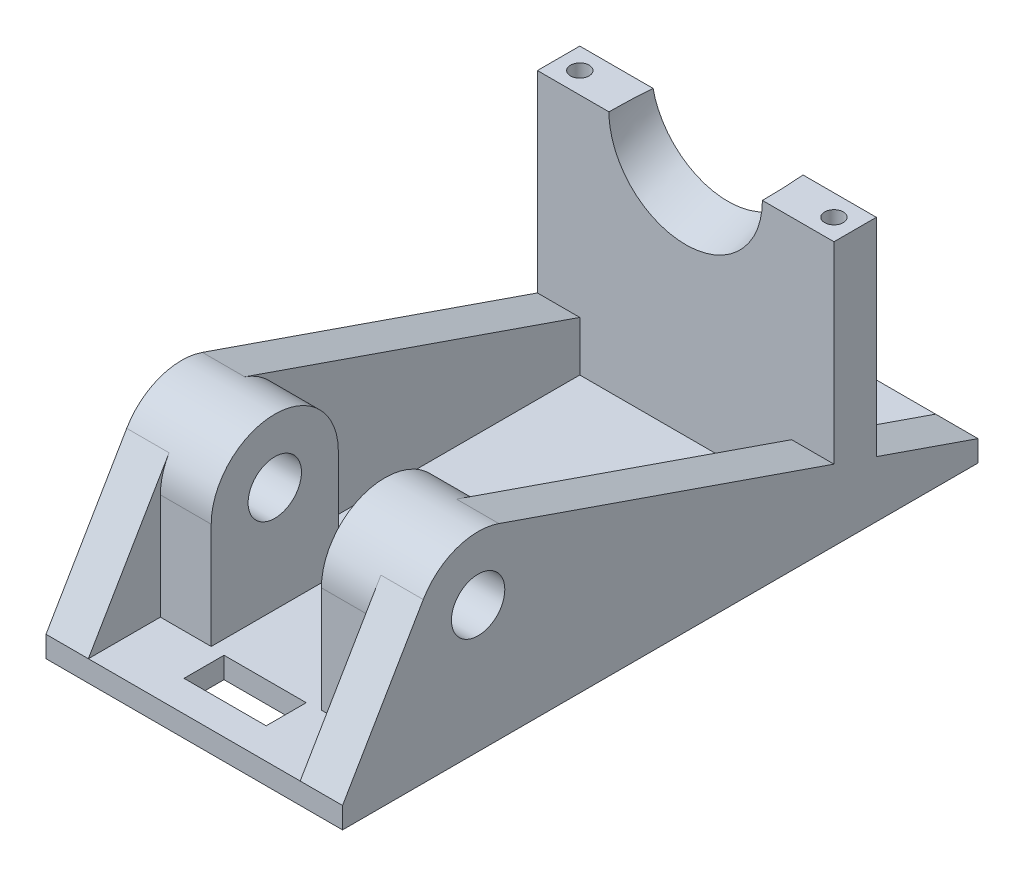
SolidWorks part; units mm, degrees
ref_plane "Front Plane" through (0, 0, 0) normal (0, 0, 1) x (1, 0, 0)
ref_plane "Top Plane" through (0, 0, 0) normal (0, 1, 0) x (1, 0, 0)
ref_plane "Right Plane" through (0, 0, 0) normal (1, 0, 0) x (0, 0, -1)
sketch "Sketch1" plane through (0, 0, 0) normal (0, 1, 0) x (1, 0, 0)
  line L1 (22.225, -47.625) -> (-22.225, -47.625)
  line L2 (22.225, -47.625) -> (22.225, 47.625)
  line L3 (22.225, 47.625) -> (-22.225, 47.625)
  line L4 (-22.225, -47.625) -> (-22.225, 47.625)
  line L5 (22.225, -47.625) -> (-22.225, 47.625) construction
  line L6 (22.225, 47.625) -> (-22.225, -47.625) construction
  point P0 (0, 0)
  dimension "D1" = 95.25
  dimension "D2" = 44.45
extrude "Boss-Extrude1" add sketch "Sketch1" along normal blind 3.175
sketch "Sketch2" plane through (0, 0, 0) normal (1, 0, 0) x (0, 0, -1)
  line L3 (-47.625, 3.175) -> (-47.625, 0) construction
  line L4 (-36.83, 3.175) -> (-36.83, 19.05)
  line L5 (-24.1873, 28.0503) -> (47.625, 3.175)
  line L6 (-47.625, 3.175) -> (47.625, 3.175)
  line L7 (-47.625, 3.175) -> (-35.5269, 23.859)
  line L8 (-17.78, 3.175) -> (-17.78, 19.05)
  circle A0 centre (-27.305, 19.05) radius 4
  arc A2 (-35.5269, 23.859) -> (-24.1873, 28.0503) centre (-27.305, 19.05) cw
  arc A3 (-17.78, 19.05) -> (-36.83, 19.05) centre (-27.305, 19.05) ccw
  point P6 (-47.625, 1.5875)
  dimension "D1" = 8
  dimension "D6" = 19.05
  dimension "D2" = 20.32
  dimension "D3" = 19.05
extrude "Boss-Extrude2" add sketch "Sketch2" along normal mid plane 44.45 contours A2 L6 L5 | A2 A0 | A3 L7 L6 L4 region at (0, 9.3974, 40.4061) region at (0, 14.4275, 27.305) region at (0, 10.8864, -3.7601)
extrude "Cut-Extrude1" cut sketch "Sketch2<3>" against normal mid plane 31.75 contours A3 L7 L6 L4 | A3 L8 L6 L5 region at (0, 9.3974, 40.4061) region at (0, 10.8864, -3.7601)
sketch "Sketch2<3>" plane through (0, 0, 0) normal (1, 0, 0) x (0, 0, -1) same geometry as "Sketch2"
extrude "Cut-Extrude2" cut sketch "Sketch2<4>" against normal mid plane 16.51 contours A2 A0 | A0 region at (0, 14.4275, 27.305) region at (0, 19.05, 27.305)
sketch "Sketch2<4>" plane through (0, 0, 0) normal (1, 0, 0) x (0, 0, -1) same geometry as "Sketch2"
sketch "Sketch3" plane through (0, 3.175, 0) normal (0, 1, 0) x (1, 0, 0)
  line L0 (-15.875, 0) -> (15.875, 0) construction
  line L5 (-15.875, -24.1873) -> (-15.875, 47.625) construction
  line L6 (15.875, -17.78) -> (15.875, 47.625) construction
  line L8 (-6.1595, 43.005) -> (6.1595, 43.005)
  line L9 (-6.1595, 43.005) -> (-6.1595, 37.005)
  line L10 (-6.1595, 37.005) -> (6.1595, 37.005)
  line L11 (6.1595, 43.005) -> (6.1595, 37.005)
  line L12 (-6.1595, 43.005) -> (6.1595, 37.005) construction
  line L13 (6.1595, 43.005) -> (-6.1595, 37.005) construction
  line L14 (-15.875, 47.625) -> (15.875, 47.625) construction
  line L15 (-6.1595, -37.005) -> (6.1595, -37.005)
  line L16 (6.1595, -43.005) -> (6.1595, -37.005)
  line L17 (-6.1595, -43.005) -> (6.1595, -43.005)
  line L18 (-6.1595, -43.005) -> (-6.1595, -37.005)
  point P11 (0, 37.005)
  point P12 (0, 40.005)
  dimension "D1" = 12.319
  dimension "D2" = 6
  dimension "D3" = 7.62
extrude "Cut-Extrude3" cut sketch "Sketch3" against normal through all
sketch "Sketch4" plane through (0, 3.175, 0) normal (0, 1, 0) x (1, 0, 0)
  line L0 (-22.225, -24.1873) -> (-22.225, 47.625) construction
  line L1 (-22.225, 32.385) -> (22.225, 32.385)
  line L2 (-22.225, 32.385) -> (-22.225, 26.035)
  line L3 (-22.225, 26.035) -> (22.225, 26.035)
  line L4 (22.225, 32.385) -> (22.225, 26.035)
  line L5 (22.225, -24.1873) -> (22.225, 47.625) construction
  line L6 (-6.1595, 43.005) -> (-6.1595, 37.005) construction
  point P10 (-6.1595, 40.005)
  dimension "D1" = 7.62
  dimension "D2" = 6.35
extrude "Boss-Extrude3" add sketch "Sketch4" along normal blind 55.88
ref_plane "Plane1" through (0, 0, 0) normal (1, 0, 0) x (0, 0, -1)
sketch "Sketch5" plane through (0, 0, 0) normal (1, 0, 0) x (0, 0, -1)
  line L0 (-27.305, 19.05) -> (48.895, 19.05) construction
  line L1 (-27.305, 19.05) -> (43.8338, 46.3576)
  dimension "D1" = 76.2
  dimension "D2" = 76.2
  dimension "D3" = 21
sketch "Sketch6" plane through (0, 0, -26.035) normal (0, 0, 1) x (1, 0, 0)
  circle A0 centre (0, 39.5253) radius 11.5
  point P0 (0, 39.5253)
  dimension "D1" = 23
sweep "Cut-Sweep1" cut profiles "Sketch6" path "Sketch5"
sketch "Sketch10" plane through (0, 0, -26.035) normal (0, 0, 1) x (1, 0, 0)
  line L1 (-22.225, 59.055) -> (-22.225, 10.6536) construction
  line L2 (22.225, 59.055) -> (22.225, 10.6536) construction
  line L4 (-22.225, 39.5253) -> (-15.31, 39.5253)
  line L5 (15.31, 39.5253) -> (22.225, 39.5253)
  line L6 (-22.225, 39.5253) -> (-22.225, 59.055)
  line L7 (-22.225, 59.055) -> (22.225, 59.055)
  line L8 (22.225, 59.055) -> (22.225, 39.5253)
  circle A3 centre (0, 39.5253) radius 11.5 construction
  arc A4 (15.31, 39.5253) -> (-15.31, 39.5253) centre (0, 39.5253) ccw
  dimension "D2" = 3.81
sweep "Cut-Sweep4" cut profiles "Sketch10" path "Sketch5<4>"
sketch "Sketch5<4>" plane through (0, 0, 0) normal (1, 0, 0) x (0, 0, -1) same geometry as "Sketch5"
sketch "Sketch11" plane through (0, 0, -26.035) normal (0, 0, 1) x (1, 0, 0)
  line L0 (22.225, 39.5253) -> (22.225, 10.6536) construction
  line L1 (-22.225, 39.5253) -> (22.225, 39.5253)
  line L2 (-22.225, 39.5253) -> (-22.225, 47.1453)
  line L3 (-22.225, 47.1453) -> (22.225, 47.1453)
  line L4 (22.225, 39.5253) -> (22.225, 47.1453)
  arc A0 (15.31, 39.5253) -> (13.279, 47.1453) centre (0, 39.5253) ccw
  arc A1 (-13.279, 47.1453) -> (-15.31, 39.5253) centre (0, 39.5253) ccw
  line M6 (-15.31, 39.5253) -> (-22.225, 39.5253)
  line M14 (22.225, 39.5253) -> (15.31, 39.5253)
  arc M15 (15.31, 39.5253) -> (-15.31, 39.5253) centre (0, 39.5253) ccw
  dimension "D1" = 7.62
extrude "Boss-Extrude4" add sketch "Sketch11" against normal blind 6.35 contours L3 L2 M6 M15 | L4 L3 M14 M15 region at (-18.4148, 43.5031, -26.035) region at (18.4148, 43.5031, -26.035)
sketch "Sketch12" plane through (0, 47.1453, 0) normal (0, 1, 0) x (1, 0, 0)
  line L0 (-22.225, 32.385) -> (-22.225, 26.035) construction
  line L1 (-22.225, 32.385) -> (-15.875, 32.385) construction
  line L2 (0, 0) -> (0, 50.8)
  circle A0 centre (-19.05, 29.21) radius 1.4
  circle A1 centre (19.05, 29.21) radius 1.4
  dimension "D3" = 2.8
  dimension "D1" = 3.175
  dimension "D2" = 3.175
  dimension "D4" = 50.8
extrude "Cut-Extrude4" cut sketch "Sketch12" against normal blind 18.75 contours A0 | A1 region at (-19.05, 47.1453, -29.21) region at (19.05, 47.1453, -29.21)
chamfer "Chamfer1" distance 4.83 distance2 4.32 2 edges at (19.05, 47.1453, -27.81) (-19.05, 47.1453, -27.81) first distance on face at (19.05, 28.3953, -27.81) first distance on face at (-19.05, 47.1453, -27.81)
sketch "Sketch13" plane through (0, 0, -26.035) normal (0, 0, 1) x (1, 0, 0)
  line L1 (-27.9424, 39.5253) -> (29.3265, 39.5253)
  line L2 (-27.9424, 39.5253) -> (-27.9424, 59.1987)
  line L3 (-27.9424, 59.1987) -> (29.3265, 59.1987)
  line L4 (29.3265, 39.5253) -> (29.3265, 59.1987)
extrude "Cut-Extrude5" cut sketch "Sketch13" against normal through all both and the other way through all
